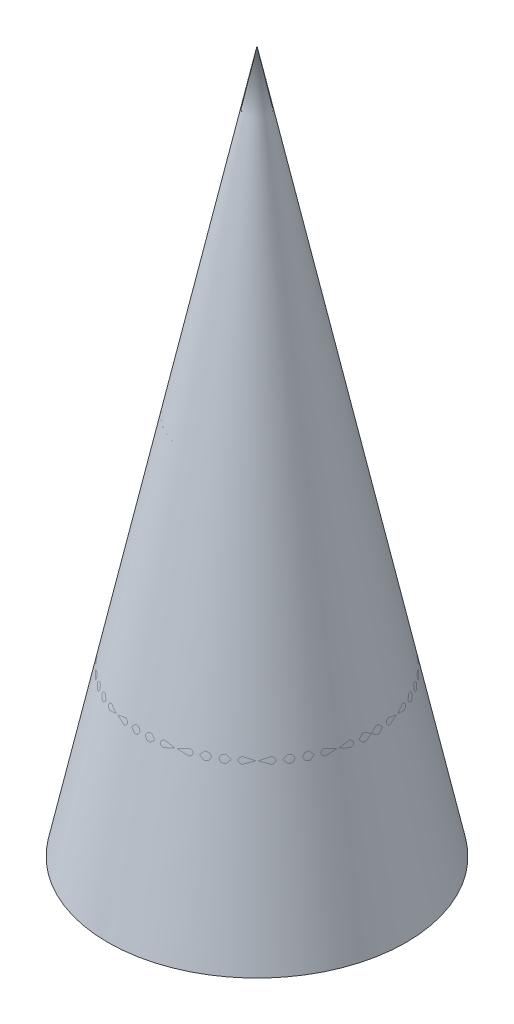
SolidWorks part; units mm, degrees
ref_plane "前视基准面" through (0, 0, 0) normal (0, 0, 1) x (1, 0, 0)
ref_plane "上视基准面" through (0, 0, 0) normal (0, 1, 0) x (1, 0, 0)
ref_plane "右视基准面" through (0, 0, 0) normal (1, 0, 0) x (0, 0, -1)
sketch "草图1" plane through (0, 0, 0) normal (0, 0, 1) x (1, 0, 0)
  line L0 (0, 0) -> (0, 300)
  line L1 (0, 300) -> (63.767, 0)
  line L2 (63.767, 0) -> (0, 0)
  line L3 (0, 118.336) -> (0, -13.1932) construction
  dimension "D1" = 12
  dimension "D2" = 300
revolve "旋转1" add sketch "草图1" angle 360 about L3
sketch "草图2" plane through (0, 0, 0) normal (0, 0, 1) x (1, 0, 0)
  line L1 (0, 300) -> (0, -122.298) construction
  line L2 (0, 185.703) -> (0, 125.713)
  line L3 (0, 109.5083) -> (0, 9.5183)
  arc A0 (0, 125.713) -> (0, 185.703) centre (0, 155.708) ccw
  arc A1 (0, 9.5183) -> (0, 109.5083) centre (0, 59.5133) ccw
  dimension "D1" = 59.99
  dimension "D2" = 99.99
  dimension "D3" = 144.292
  dimension "D4" = 240.4867
revolve "切除-旋转1" cut sketch "草图2" angle 360 about L1
